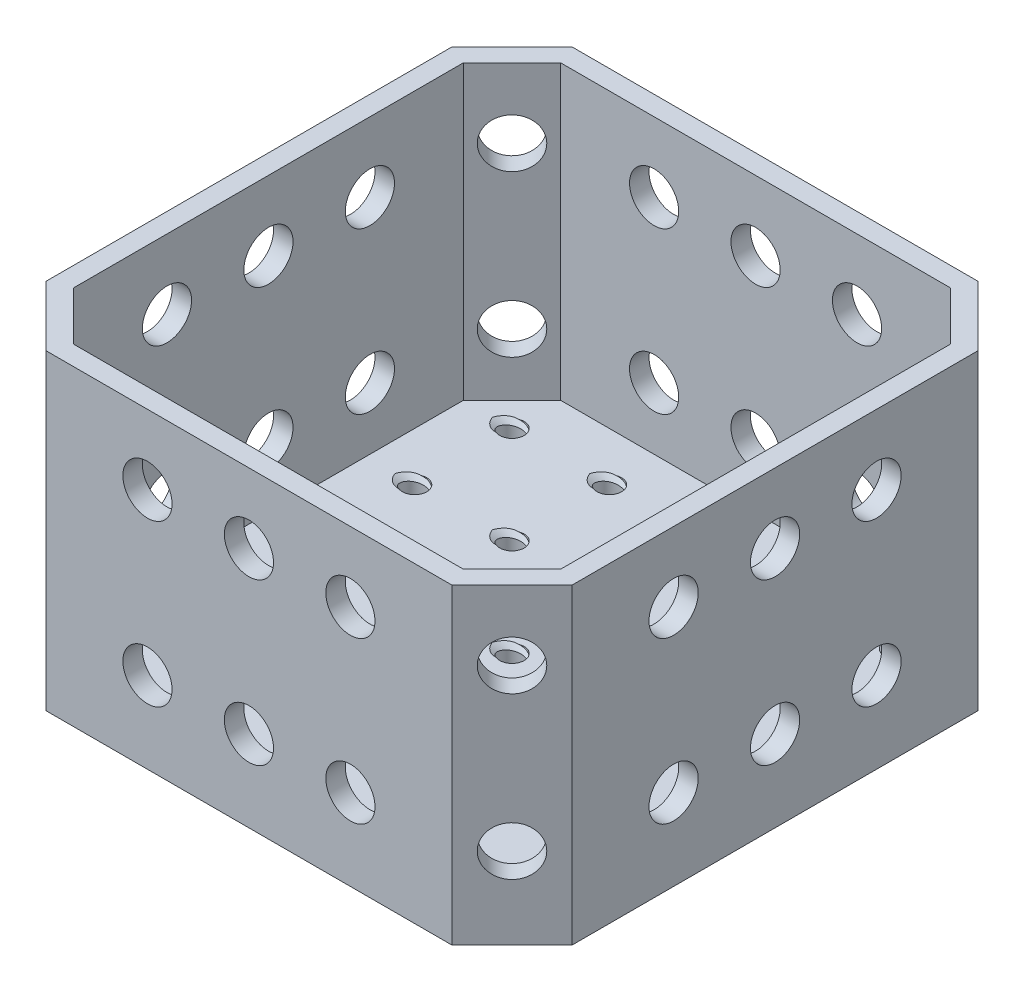
SolidWorks part; units mm, degrees
ref_plane "Front Plane" through (0, 0, 0) normal (0, 0, 1) x (1, 0, 0)
ref_plane "Top Plane" through (0, 0, 0) normal (0, 1, 0) x (1, 0, 0)
ref_plane "Right Plane" through (0, 0, 0) normal (1, 0, 0) x (0, 0, -1)
sketch "Sketch1" plane through (0, 0, 0) normal (0, 1, 0) x (1, 0, 0)
  line L0 (0, 90) -> (10, 100)
  line L1 (10, 0) -> (90, 0)
  line L2 (0, 10) -> (0, 90)
  line L3 (10, 100) -> (90, 100)
  line L4 (100, 10) -> (100, 90)
  line L5 (10, 0) -> (0, 10)
  line L6 (90, 0) -> (100, 10)
  line L7 (90, 100) -> (100, 90)
  line L8 (8.3431, 104) -> (91.6569, 104)
  line L9 (91.6569, 104) -> (104, 91.6569)
  line L10 (104, 8.3431) -> (104, 91.6569)
  line L11 (91.6569, -4) -> (104, 8.3431)
  line L12 (8.3431, -4) -> (91.6569, -4)
  line L13 (8.3431, -4) -> (-4, 8.3431)
  line L14 (-4, 8.3431) -> (-4, 91.6569)
  line L15 (-4, 91.6569) -> (8.3431, 104)
  point P0 (0, 0)
  point P1 (100, 100)
  point P2 (0, 100)
  point P3 (100, 0)
  dimension "D1" = 100
  dimension "D2" = 100
  dimension "D3" = 4
extrude "Boss-Extrude1" add sketch "Sketch1" along normal blind 60
sketch "Sketch2" plane through (0, 0, 0) normal (0, -1, 0) x (1, 0, 0)
  line L0 (-4, -91.6569) -> (-4, -8.3431) construction
  line L1 (8.3431, -104) -> (-4, -91.6569) construction
  line L2 (91.6569, -104) -> (8.3431, -104) construction
  line L3 (104, -91.6569) -> (91.6569, -104) construction
  line L4 (104, -8.3431) -> (104, -91.6569) construction
  line L5 (91.6569, 4) -> (104, -8.3431) construction
  line L6 (8.3431, 4) -> (91.6569, 4) construction
  line L7 (-4, -8.3431) -> (8.3431, 4) construction
  line L8 (-4, -91.6569) -> (-4, -8.3431)
  line L9 (8.3431, -104) -> (-4, -91.6569)
  line L10 (91.6569, -104) -> (8.3431, -104)
  line L11 (104, -91.6569) -> (91.6569, -104)
  line L12 (104, -8.3431) -> (104, -91.6569)
  line L13 (91.6569, 4) -> (104, -8.3431)
  line L14 (8.3431, 4) -> (91.6569, 4)
  line L15 (-4, -8.3431) -> (8.3431, 4)
extrude "Boss-Extrude2" add sketch "Sketch2" along normal blind 4
sketch "Sketch3" plane through (0, 0, 0) normal (0, 1, 0) x (1, 0, 0)
  line L0 (5, 95) -> (95, 95) construction
  line L1 (10, 100) -> (0, 90) construction
  line L2 (100, 90) -> (90, 100) construction
  line L3 (5, 95) -> (95, 5) construction
  line L4 (90, 0) -> (100, 10) construction
  line L5 (0, 50) -> (100, 50) construction
  line L6 (0, 90) -> (0, 10) construction
  line L7 (100, 10) -> (100, 90) construction
  line L8 (95, 95) -> (5, 5) construction
  line L9 (0, 10) -> (10, 0) construction
  circle A0 centre (10, 90) radius 2.5
  circle A1 centre (30, 90) radius 2.5
  circle A2 centre (50, 90) radius 2.5
  circle A3 centre (70, 90) radius 2.5
  circle A4 centre (90, 90) radius 2.5
  circle A5 centre (10, 70) radius 2.5
  circle A6 centre (30, 70) radius 2.5
  circle A7 centre (50, 70) radius 2.5
  circle A8 centre (70, 70) radius 2.5
  circle A9 centre (90, 70) radius 2.5
  circle A10 centre (10, 50) radius 2.5
  circle A11 centre (30, 50) radius 2.5
  circle A12 centre (50, 50) radius 2.5
  circle A13 centre (70, 50) radius 2.5
  circle A14 centre (90, 50) radius 2.5
  circle A15 centre (10, 30) radius 2.5
  circle A16 centre (30, 30) radius 2.5
  circle A17 centre (50, 30) radius 2.5
  circle A18 centre (70, 30) radius 2.5
  circle A19 centre (90, 30) radius 2.5
  circle A20 centre (10, 10) radius 2.5
  circle A21 centre (30, 10) radius 2.5
  circle A22 centre (50, 10) radius 2.5
  circle A23 centre (70, 10) radius 2.5
  circle A24 centre (90, 10) radius 2.5
  dimension "D1" = 5
  dimension "D3" = 20
  dimension "D5" = 20
  dimension "D2" = 5
  dimension "D4" = 5
extrude "Cut-Extrude1" cut sketch "Sketch3" against normal blind 26
sketch "Sketch4" plane through (0, 0, 0) normal (0, 1, 0) x (1, 0, 0)
  circle A0 centre (10, 90) radius 2.5 construction
  circle A1 centre (10, 90) radius 2.5
curve "Helix/Spiral1" pitch 4 height 4 turns 1
ref_plane "Plane1" through (0, 0, -90) normal (0, 0, -1) x (-1, 0, 0)
sketch "Sketch5" plane through (0, 0, -90) normal (0, 0, -1) x (-1, 0, 0)
  line L0 (-7.5, 0) -> (-7.5, 0.75)
  line L1 (-7.5, -4) -> (-7.5, 0) construction
  line L2 (-7.5, -4) -> (-7.5, 0) construction
  line L3 (-7.5, 0.75) -> (-6, 0)
  line L4 (0, 0) -> (-10, 0) construction
  line L5 (-6, 0) -> (-7.5, -0.75)
  line L6 (-7.5, -0.75) -> (-7.5, 0)
  point P6 (-7.5, 0)
  point P11 (-7.5, 0)
  point P12 (-7.5, 0.0141)
  point P13 (-7.5, 0)
  point P14 (0, 0)
  point P15 (0, 0)
  dimension "D1" = 0.75
  dimension "D2" = 1.5
sweep "Cut-Sweep1" cut profiles "Sketch5" path "Helix/Spiral1" align with end faces yes
pattern_linear "LPattern2" count 5 spacing 20 along (-1, 0, 0) count 5 spacing 20 along (0, 0, 1) of "Cut-Sweep1"
sketch "Sketch6" plane through (2.1716, 0, -2.1716) normal (-0.7071, 0, 0.7071) x (0.7071, 0, 0.7071)
  line L0 (0, 60) -> (0, -4) construction
  line L1 (-8.7279, 60) -> (8.7279, 60) construction
  line L2 (8.7279, -4) -> (-8.7279, -4) construction
  circle A0 centre (0, 12.7) radius 5.05
  circle A1 centre (0, 45.7) radius 5.05
  dimension "D1" = 10.1
  dimension "D2" = 16.7
  dimension "D3" = 33
extrude "Cut-Extrude2" cut sketch "Sketch6" against normal blind 184
sketch "Sketch7" plane through (47.8284, 0, 47.8284) normal (0.7071, 0, 0.7071) x (0.7071, 0, -0.7071)
  line L0 (70.7107, 60) -> (70.7107, -4) construction
  line L1 (61.9828, 60) -> (79.4386, 60) construction
  line L2 (79.4386, -4) -> (61.9828, -4) construction
  circle A0 centre (70.7107, 12.7) radius 5.05
  circle A1 centre (70.7107, 45.7) radius 5.05
  point P10 (0, 0)
  point P11 (0, 0)
  point P12 (0, 0)
  dimension "D1" = 10.1
  dimension "D2" = 33
  dimension "D3" = 16.7
extrude "Cut-Extrude3" cut sketch "Sketch7" against normal blind 184
sketch "Sketch8" plane through (-4, 0, 0) normal (-1, 0, 0) x (0, 0, 1)
  line L0 (-50, 60) -> (-50, -4) construction
  line L1 (-91.6569, 60) -> (-8.3431, 60) construction
  line L2 (-8.3431, -4) -> (-91.6569, -4) construction
  line L3 (-50, 28) -> (-91.6569, 28) construction
  line L4 (-91.6569, 60) -> (-91.6569, -4) construction
  line L5 (-70.8284, -4) -> (-70.8284, 60) construction
  circle A0 centre (-50, 45.7) radius 5.05
  circle A1 centre (-50, 12.7) radius 5.05
  circle A2 centre (-70.8284, 45.7) radius 5.05
  circle A3 centre (-70.8284, 12.7) radius 5.05
  circle A4 centre (-29.1716, 12.7) radius 5.05
  circle A5 centre (-29.1716, 45.7) radius 5.05
  point P17 (-70.8284, 28)
  point P21 (0, 0)
  point P22 (0, 0)
  dimension "D1" = 10.1
  dimension "D2" = 16.7
  dimension "D3" = 33
extrude "Cut-Extrude4" cut sketch "Sketch8" against normal blind 184
sketch "Sketch9" plane through (0, 0, -104) normal (0, 0, -1) x (-1, 0, 0)
  line L0 (-50, 60) -> (-50, -4) construction
  line L1 (-91.6569, 60) -> (-8.3431, 60) construction
  line L2 (-8.3431, -4) -> (-91.6569, -4) construction
  line L3 (-50, 28) -> (-91.6569, 28) construction
  line L4 (-91.6569, 60) -> (-91.6569, -4) construction
  line L5 (-70.8284, -4) -> (-70.8284, 60) construction
  circle A0 centre (-50, 45.7) radius 5.05
  circle A1 centre (-70.8284, 45.7) radius 5.05
  circle A2 centre (-50, 12.7) radius 5.05
  circle A3 centre (-70.8284, 12.7) radius 5.05
  circle A4 centre (-29.1716, 12.7) radius 5.05
  circle A5 centre (-29.1716, 45.7) radius 5.05
  point P13 (-70.8284, 28)
  point P21 (0, 0)
  point P22 (0, 0)
  dimension "D1" = 10.1
  dimension "D2" = 16.7
  dimension "D3" = 33
extrude "Cut-Extrude5" cut sketch "Sketch9" against normal blind 184
